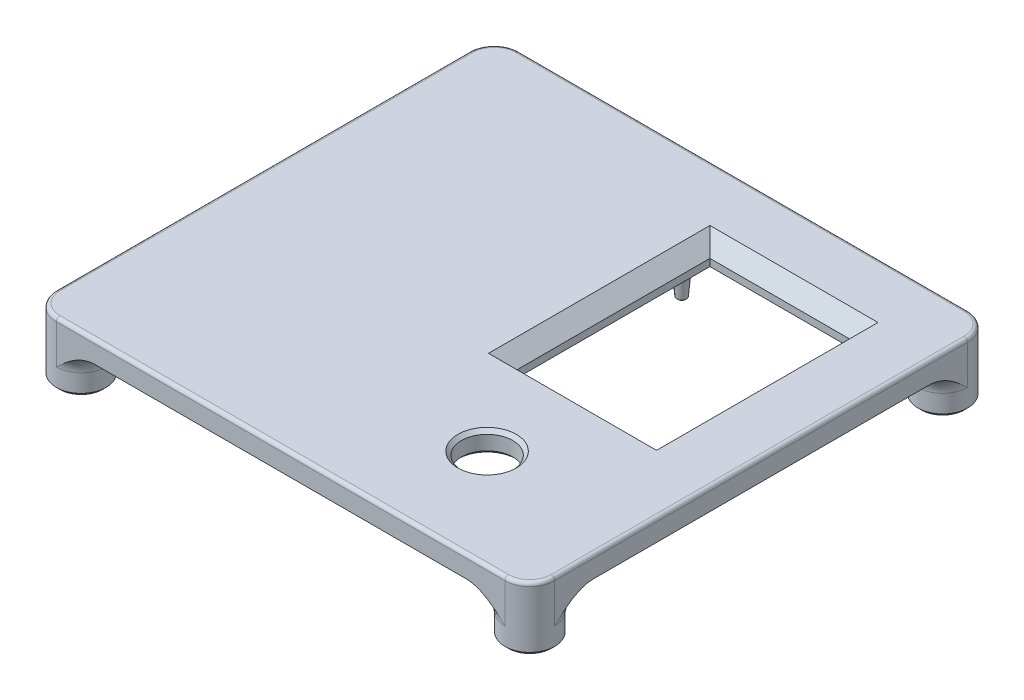
SolidWorks part; units mm, degrees
ref_plane "Front Plane" through (0, 0, 0) normal (0, 0, 1) x (1, 0, 0)
ref_plane "Top Plane" through (0, 0, 0) normal (0, 1, 0) x (1, 0, 0)
ref_plane "Right Plane" through (0, 0, 0) normal (1, 0, 0) x (0, 0, -1)
sketch "Sketch1" plane through (0, 0, 0) normal (0, 1, 0) x (1, 0, 0)
  line L1 (0, 0) -> (70, 0)
  line L2 (0, 0) -> (0, 65)
  line L3 (0, 65) -> (70, 65)
  line L4 (70, 0) -> (70, 65)
  dimension "D1" = 70
  dimension "D2" = 65
extrude "Boss-Extrude1" add sketch "Sketch1" along normal blind 3
fillet "Fillet1" radius 3.5 4 edges at (70, 1.5, -65) (70, 1.5, 0) (0, 1.5, 0) (0, 1.5, -65)
sketch "Sketch2" plane through (0, 0, 0) normal (0, -1, 0) x (1, 0, 0)
  line L0 (35, 0) -> (35, -65) construction
  line L1 (3.5, 0) -> (66.5, 0) construction
  line L2 (66.5, -65) -> (3.5, -65) construction
  line L3 (0, -32.5) -> (70, -32.5) construction
  line L4 (0, -61.5) -> (0, -3.5) construction
  line L5 (70, -3.5) -> (70, -61.5) construction
  circle A0 centre (3.5, -61.5) radius 3.5
  dimension "D1" = 7
extrude "Boss-Extrude2" add sketch "Sketch2" along normal blind 6
sketch "Sketch5" plane through (0, -6, 0) normal (0, -1, 0) x (1, 0, 0)
  circle A0 centre (3.5, -61.5) radius 2
  dimension "D1" = 4
extrude "Cut-Extrude1" cut sketch "Sketch5" against normal blind 5.5 contours A0
chamfer "Chamfer1" distance 0.5 angle 45 2 edges at (3.5, -6, -63.5) (3.5, -6, -65)
pattern_linear "LPattern1" count 2 spacing 63 along (1, 0, 0) count 2 spacing 58 along (0, 0, 1) of "Boss-Extrude2", "Cut-Extrude1", "Chamfer1"
sketch "Sketch6" plane through (0, 0, 0) normal (0, -1, 0) x (1, 0, 0)
  line L0 (0, -61.5) -> (0, -3.5) construction
  line L1 (10, -15) -> (23.7, -15) construction
  line L2 (23.7, -15) -> (16.85, -15) construction
  line L3 (16.85, -15) -> (16.85, -43.3821) construction
  line L4 (3.5, 0) -> (66.5, 0) construction
  circle A0 centre (10, -15) radius 3
  circle A1 centre (23.7, -15) radius 3
  circle A2 centre (16.85, -43.3821) radius 3
  circle A3 centre (10, -15) radius 1.6
  circle A4 centre (23.7, -15) radius 1.6
  circle A5 centre (16.85, -43.3821) radius 1.6
  point P10 (0, 0)
  dimension "D1" = 10
  dimension "D2" = 13.7
  dimension "D3" = 28.3821
  dimension "D4" = 15
extrude "Boss-Extrude3" add sketch "Sketch6" along normal blind 5
fillet "Fillet2" radius 3 7 edges at (16.85, 0, -46.3821) (23.7, 0, -18) (10, 0, -18) (64.0251, 0, -5.9749) (64.0251, 0, -59.0251) (5.9749, 0, -59.0251) (5.9749, 0, -5.9749)
chamfer "Chamfer2" distance 0.25 angle 45 3 edges at (16.85, -5, -44.9821) (23.7, -5, -16.6) (10, -5, -16.6)
chamfer "Chamfer3" distance 0.5 angle 45 3 edges at (16.85, -5, -46.3821) (23.7, -5, -18) (10, -5, -18)
sketch "Sketch7" plane through (0, 0, 0) normal (0, -1, 0) x (1, 0, 0)
  line L0 (8.9772, 0) -> (61.0228, 0) construction
  line L1 (0, -56.0228) -> (0, -8.9772) construction
  line L2 (50, -14) -> (50, 25.0689) construction
  line L3 (40.2, -28) -> (59.8, -28)
  line L4 (40.2, -28) -> (40.2, -55.1)
  line L5 (40.2, -55.1) -> (59.8, -55.1)
  line L6 (59.8, -28) -> (59.8, -55.1)
  line L7 (50, -28) -> (50, -55.1) construction
  circle A0 centre (50, -14) radius 3.6
  dimension "D1" = 14
  dimension "D2" = 50
  dimension "D3" = 27.1
  dimension "D4" = 19.6
  dimension "D5" = 28
extrude "Cut-Extrude2" cut sketch "Sketch7" against normal through all
chamfer "Chamfer4" distance 0.5 angle 45 2 edges at (50, 0, -17.6) (50, 3, -17.6)
chamfer "Chamfer5" distance 2 angle 45 4 edges at (50, 3, -28) (59.8, 3, -41.55) (50, 3, -55.1) (40.2, 3, -41.55)
fillet "Fillet6" radius 0.5 8 edges at (1.0251, 3, -63.9749) (0, 3, -32.5) (1.0251, 3, -1.0251) (35, 3, 0) (68.9749, 3, -1.0251) (70, 3, -32.5) (68.9749, 3, -63.9749) (35, 3, -65)
sketch "Sketch8" plane through (0, 0, 0) normal (0, -1, 0) x (1, 0, 0)
  line L0 (38.075, -53.25) -> (38.075, -29.85) construction
  line L1 (50, -28) -> (50, -55.1) construction
  line L3 (59.8, -28) -> (40.2, -28) construction
  line L4 (40.2, -55.1) -> (59.8, -55.1) construction
  line L5 (40.2, -41.55) -> (59.8, -41.55) construction
  line L8 (61.925, -29.85) -> (61.925, -53.25) construction
  line L9 (40.2, -28) -> (40.2, -55.1) construction
  line L10 (59.8, -55.1) -> (59.8, -28) construction
  line L11 (38.075, -41.55) -> (61.925, -41.55) construction
  line L12 (50, -41.55) -> (50, -27.1029) construction
  circle A0 centre (38.075, -53.25) radius 1
  circle A1 centre (61.925, -53.25) radius 1
  circle A2 centre (61.925, -29.85) radius 1
  circle A3 centre (38.075, -29.85) radius 1
  dimension "D1" = 23.85
  dimension "D2" = 23.4
extrude "Boss-Extrude4" add sketch "Sketch8" along normal blind 4 draft 5
chamfer "Chamfer7" distance 0.25 angle 45 4 edges at (38.075, -4, -53.9) (61.925, -4, -53.9) (61.925, -4, -30.5) (38.075, -4, -30.5) first distance on face at (38.075, -4, -53.9) first distance on face at (61.925, -4, -53.9) first distance on face at (61.925, -4, -30.5) first distance on face at (38.075, -4, -30.5)
sketch "Sketch10" plane through (0, 0, 0) normal (0, -1, 0) x (1, 0, 0)
  line L0 (38.075, -29.85) -> (38.075, -53.25) construction
  line L1 (38.075, -53.25) -> (38.075, -41.55) construction
  line L2 (38.075, -41.55) -> (61.7839, -41.55) construction
  line L3 (61.7839, -41.55) -> (61.925, -29.85) construction
  line L4 (61.925, -29.85) -> (61.925, -53.25) construction
  line L6 (38.825, -46.55) -> (37.325, -46.55)
  line L7 (38.825, -46.55) -> (38.825, -36.55)
  line L8 (38.825, -36.55) -> (37.325, -36.55)
  line L9 (37.325, -46.55) -> (37.325, -36.55)
  line L10 (38.825, -46.55) -> (37.325, -36.55) construction
  line L11 (38.825, -36.55) -> (37.325, -46.55) construction
  line L12 (62.5339, -46.55) -> (61.0339, -46.55)
  line L13 (62.5339, -46.55) -> (62.5339, -36.55)
  line L14 (62.5339, -36.55) -> (61.0339, -36.55)
  line L15 (61.0339, -46.55) -> (61.0339, -36.55)
  line L16 (62.5339, -46.55) -> (61.0339, -36.55) construction
  line L17 (62.5339, -36.55) -> (61.0339, -46.55) construction
  dimension "D1" = 10
  dimension "D2" = 1.5
extrude "Cut-Extrude4" cut sketch "Sketch10" against normal blind 2 draft 10
equation "\"display_post_radius\"= 1mm"
